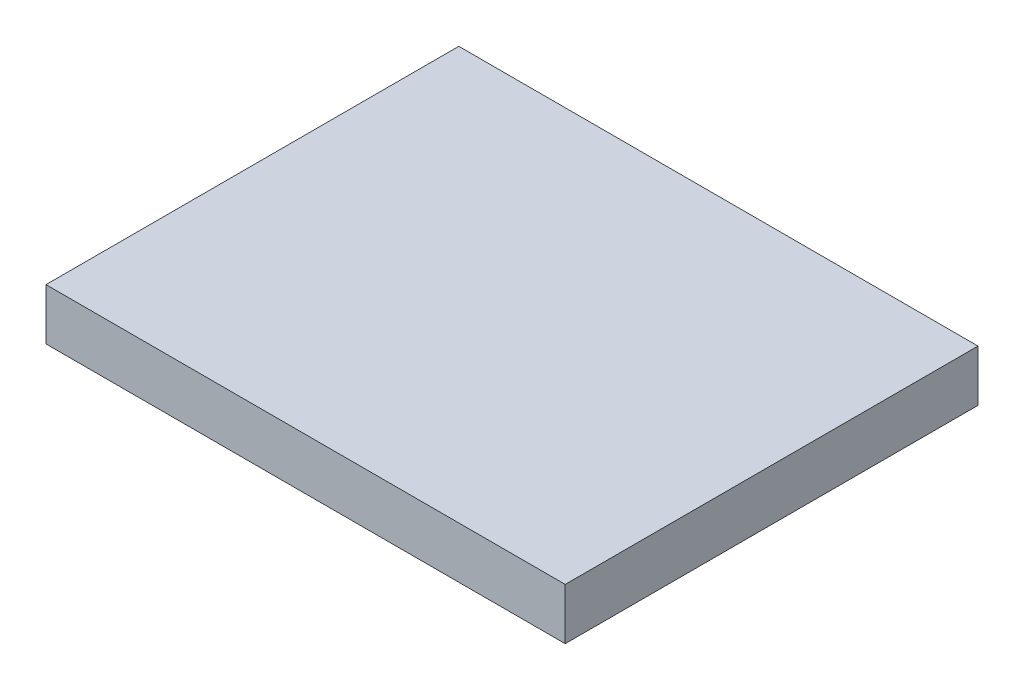
SolidWorks part; units mm, degrees
ref_plane "Front Plane" through (0, 0, 0) normal (0, 0, 1) x (1, 0, 0)
ref_plane "Top Plane" through (0, 0, 0) normal (0, 1, 0) x (1, 0, 0)
ref_plane "Right Plane" through (0, 0, 0) normal (1, 0, 0) x (0, 0, -1)
sketch "Sketch1" plane through (0, 0, 0) normal (0, 1, 0) x (1, 0, 0)
  line L1 (0, 0) -> (283, 0)
  line L2 (0, 0) -> (0, 225)
  line L3 (0, 225) -> (283, 225)
  line L4 (283, 0) -> (283, 225)
  dimension "D1" = 225
  dimension "D2" = 283
extrude "Boss-Extrude1" add sketch "Sketch1" along normal blind 28
equation "\"Length\" = 283mm"
equation "\"Width\" = 225mm"
equation "\"WallThickness\" = 12.5mm"
equation "\"D1@Sketch1\"=\"Width\""
equation "\"D2@Sketch1\"=\"Length\""
equation "\"UpperWaterJacketThickness\" = 28mm"
equation "\"D1@Boss-Extrude1\"=\"UpperWaterJacketThickness\""
